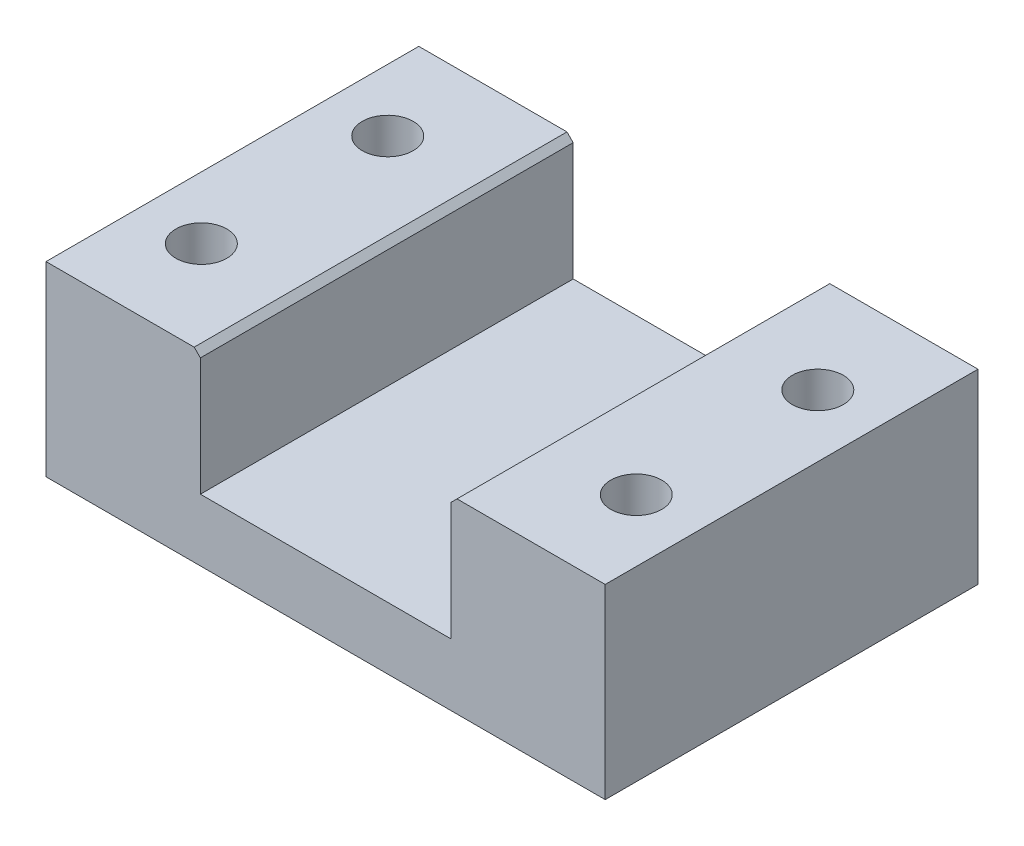
SolidWorks part; units mm, degrees
ref_plane "Спереди" through (0, 0, 0) normal (0, 0, 1) x (1, 0, 0)
ref_plane "Сверху" through (0, 0, 0) normal (0, 1, 0) x (1, 0, 0)
ref_plane "Справа" through (0, 0, 0) normal (1, 0, 0) x (0, 0, -1)
sketch "Sketch1" plane through (0, 0, 0) normal (0, 1, 0) x (1, 0, 0)
  line L1 (45, -30) -> (-45, -30)
  line L2 (45, -30) -> (45, 30)
  line L3 (45, 30) -> (-45, 30)
  line L4 (-45, -30) -> (-45, 30)
  line L5 (45, -30) -> (-45, 30) construction
  line L6 (45, 30) -> (-45, -30) construction
  point P0 (0, 0)
  dimension "D1" = 90
  dimension "D2" = 60
extrude "Boss-Extrude1" add sketch "Sketch1" along normal blind 30
sketch "Sketch2" plane through (0, 0, 30) normal (0, 0, 1) x (1, 0, 0)
  line L0 (-45, 30) -> (45, 30) construction
  line L1 (20.15, 50) -> (-20.15, 50)
  line L2 (20.15, 50) -> (20.15, 10)
  line L3 (20.15, 10) -> (-20.15, 10)
  line L4 (-20.15, 50) -> (-20.15, 10)
  line L5 (20.15, 50) -> (-20.15, 10) construction
  line L6 (20.15, 10) -> (-20.15, 50) construction
  point P0 (0, 30)
  dimension "D1" = 40.3
  dimension "D2" = 40
extrude "Cut-Extrude1" cut sketch "Sketch2" against normal through all
sketch "Sketch3" plane through (0, 0, 0) normal (0, -1, 0) x (1, 0, 0)
  line L1 (-35, -15) -> (35, -15) construction
  line L2 (-35, -15) -> (-35, 15) construction
  line L3 (-35, 15) -> (35, 15) construction
  line L4 (35, -15) -> (35, 15) construction
  line L5 (-35, -15) -> (35, 15) construction
  line L6 (-35, 15) -> (35, -15) construction
  circle A0 centre (-35, 15) radius 4.1
  circle A1 centre (-35, -15) radius 4.1
  circle A2 centre (35, -14.2173) radius 4.1
  circle A3 centre (35, 15) radius 4.1
  point P0 (0, 0)
  dimension "D3" = 8.2
  dimension "D1" = 30
  dimension "D2" = 70
extrude "Cut-Extrude2" cut sketch "Sketch3" against normal through all
sketch "Sketch4" plane through (0, 0, 0) normal (0, -1, 0) x (1, 0, 0)
  circle A0 centre (35, 15) radius 8
  circle A1 centre (35, -14.2173) radius 8
  circle A2 centre (-35, 15) radius 8
  circle A3 centre (-35, -15) radius 8
  dimension "D1" = 16
extrude "Cut-Extrude3" cut sketch "Sketch4" against normal blind 7
chamfer "Chamfer1" distance 1 angle 45 2 edges at (-20.15, 30, 0) (20.15, 30, 0)
